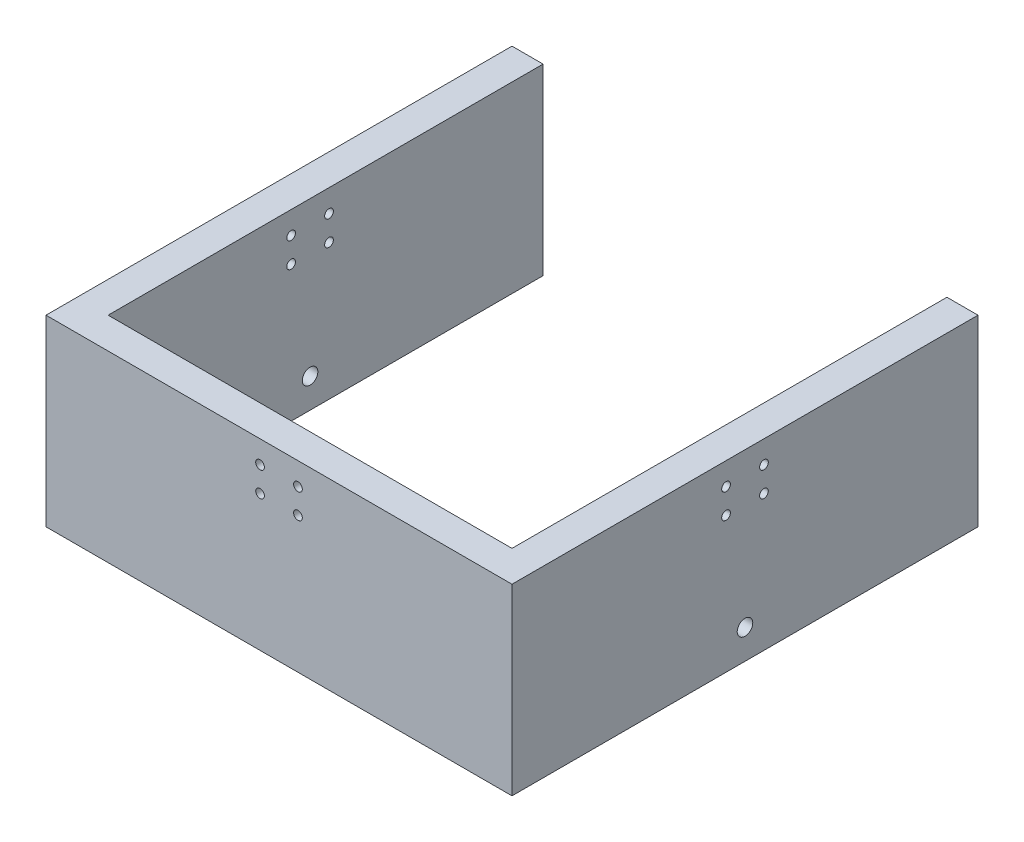
SolidWorks part; units mm, degrees
ref_plane "Front" through (0, 0, 0) normal (0, 0, 1) x (1, 0, 0)
ref_plane "Top" through (0, 0, 0) normal (0, 1, 0) x (1, 0, 0)
ref_plane "Right" through (0, 0, 0) normal (1, 0, 0) x (0, 0, -1)
sketch "Sketch1" plane through (0, 0, 0) normal (0, 1, 0) x (1, 0, 0)
  line L1 (-75, -75) -> (75, -75)
  line L2 (-75, -75) -> (-75, 75)
  line L3 (-75, 75) -> (75, 75)
  line L4 (75, -75) -> (75, 75)
  line L5 (-75, -75) -> (75, 75) construction
  line L6 (-75, 75) -> (75, -75) construction
  point P0 (0, 0)
  dimension "D1" = 150
  dimension "D2" = 150
extrude "Boss-Extrude1" add sketch "Sketch1" against normal blind 59
sketch "Sketch2" plane through (0, 0, 0) normal (0, 1, 0) x (1, 0, 0)
  line L1 (-65, -65) -> (65, -65)
  line L2 (-65, -65) -> (-65, 65)
  line L3 (-65, 65) -> (65, 65)
  line L4 (65, -65) -> (65, 65)
  line L5 (-65, -65) -> (65, 65) construction
  line L6 (-65, 65) -> (65, -65) construction
  point P0 (0, 0)
  dimension "D1" = 130
  dimension "D2" = 130
extrude "Cut-Extrude1" cut sketch "Sketch2" against normal through all
sketch "Sketch4" plane through (0, 0, -65) normal (0, 0, 1) x (1, 0, 0)
  line L3 (65, 0) -> (-65, 0) construction
  line L4 (-3.5, -17.47) -> (1.5, -17.47)
  line L5 (-3.5, -17.47) -> (-3.5, 0)
  line L6 (-3.5, 0) -> (1.5, 0)
  line L7 (1.5, -17.47) -> (1.5, 0)
  line L8 (-3.5, -17.47) -> (1.5, 0) construction
  line L9 (-3.5, 0) -> (1.5, -17.47) construction
  point P6 (-1, -8.735)
  dimension "D1" = 5
ref_axis "Axis1" through (0, 0, 0) along (0, -1, 0)
sketch "Sketch9" plane through (-75, 0, 0) normal (-1, 0, 0) x (0, 0, 1)
  line L0 (-75, 0) -> (75, 0) construction
  line L1 (0, 0) -> (7.5, 0)
  line L7 (0, 0) -> (-7.5, 0)
  circle A0 centre (-6.1, -7.25) radius 1.4
  circle A1 centre (6.1, -7.25) radius 1.4
  circle A2 centre (6.1, -15.25) radius 1.4
  circle A3 centre (-6.1, -15.25) radius 1.4
  dimension "D4" = 2.8
  dimension "D2" = 7.5
  dimension "D3" = 7.5
  dimension "D5" = 7.25
extrude "Cut-Extrude4" cut sketch "Sketch9" against normal blind 10 contours A0 | A1 | A2 | A3 region at (-75, -7.25, -6.1)
pattern_circular "CirPattern1" count 3 every 90 about axis through (0, 0, 0) along (0, -1, 0) of "Cut-Extrude4" reverse direction yes
sketch "Sketch10" plane through (0, 0, 0) normal (0, 1, 0) x (1, 0, 0)
  line L0 (-65, 65) -> (65, 65)
  line L1 (-65, 65) -> (-65, 161.3983)
  line L2 (65, 65) -> (65, 161.3983)
  line L3 (-65, 161.3983) -> (65, 161.3983)
extrude "Cut-Extrude6" cut sketch "Sketch10" against normal through all
sketch "Sketch11" plane through (75, 0, 0) normal (1, 0, 0) x (0, 0, -1)
  line L0 (-75, -59) -> (75, -59) construction
  circle A0 centre (0, -49.5) radius 2.5
  dimension "D1" = 5
  dimension "D2" = 9.5
extrude "Cut-Extrude7" cut sketch "Sketch11" against normal through all
